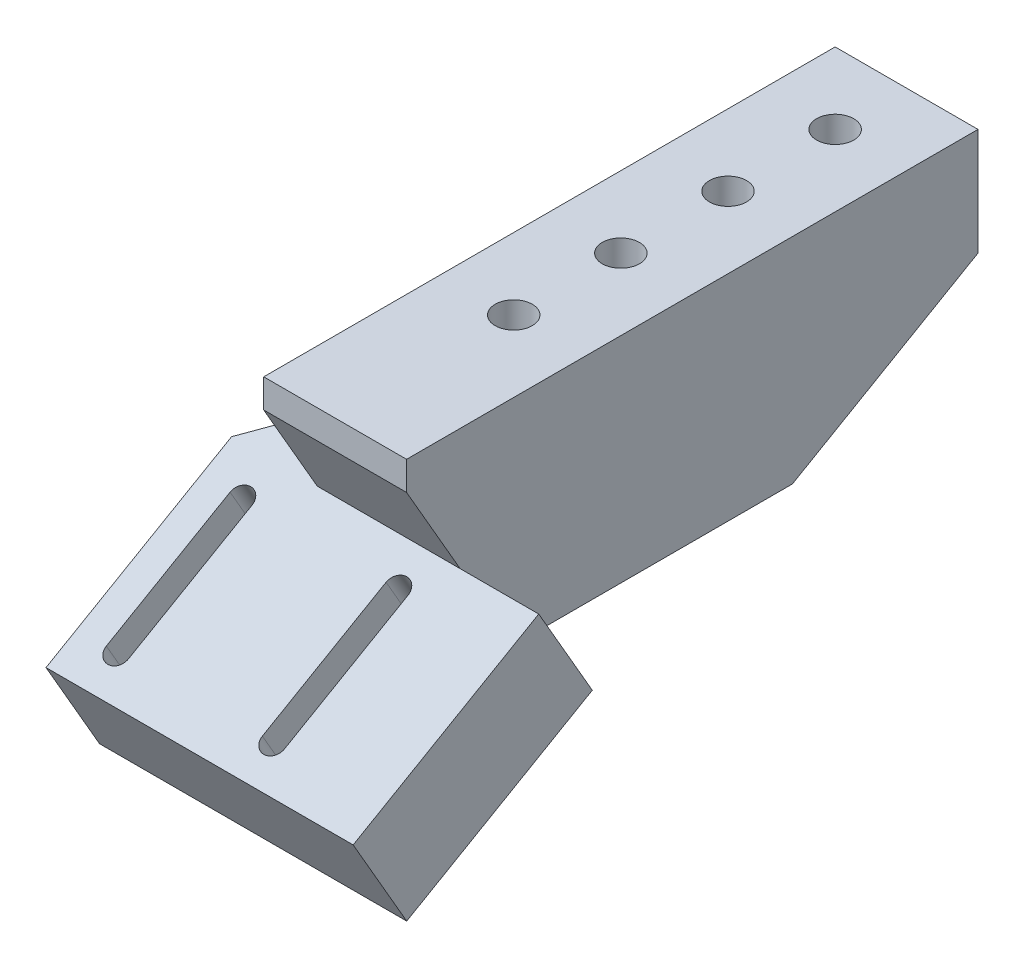
SolidWorks part; units mm, degrees
ref_plane "Front Plane" through (0, 0, 0) normal (0, 0, 1) x (1, 0, 0)
ref_plane "Top Plane" through (0, 0, 0) normal (0, 1, 0) x (1, 0, 0)
ref_plane "Right Plane" through (0, 0, 0) normal (1, 0, 0) x (0, 0, -1)
sketch "Sketch1" plane through (0, 0, 0) normal (1, 0, 0) x (0, 0, -1)
  line L1 (-40, 15) -> (40, 15)
  line L2 (-40, 15) -> (-40, -15)
  line L3 (-40, -15) -> (40, -15)
  line L4 (40, 15) -> (40, -15)
  line L5 (-40, 15) -> (40, -15) construction
  line L6 (-40, -15) -> (40, 15) construction
  point P0 (0, 0)
  dimension "D1" = 30
  dimension "D2" = 80
extrude "Boss-Extrude1" add sketch "Sketch1" against normal blind 20
chamfer "Chamfer1" distance 15 angle 60 1 edges at (-10, -15, 40) first distance on face at (-10, -15, 0)
sketch "Sketch2" plane through (0, -14.5753, 25.2452) normal (0, -0.5, 0.866) x (1, 0, 0)
  line L0 (-10, 29.5096) -> (-10, -0.4904) construction
  line L2 (-20, 29.5096) -> (0, 29.5096) construction
  line L7 (0, -0.4904) -> (-20, -0.4904) construction
  line L8 (-32, -0.4904) -> (11, -0.4904)
  line L13 (-32, -0.4904) -> (-32, 14.5096)
  line L14 (11, -0.4904) -> (11, 14.5096)
  line L15 (-32, 14.5096) -> (11, 14.5096)
  line L16 (0, 29.5096) -> (0, -0.4904) construction
  line L17 (-20, -0.4904) -> (-20, 29.5096) construction
  dimension "D1" = 11
  dimension "D2" = 12
  dimension "D3" = 15
extrude "Boss-Extrude2" add sketch "Sketch2" along normal blind 30
sketch "Sketch3" plane through (0, 12.5657, 7.2548) normal (0, 0.866, 0.5) x (1, 0, 0)
  line L0 (-26.33, -34.1506) -> (-26.33, -54.1506) construction
  line L3 (-24.78, -34.1506) -> (-24.78, -54.1506)
  line L4 (-27.88, -34.1506) -> (-27.88, -54.1506)
  line L5 (-32, -44.1506) -> (11, -44.1506) construction
  line L6 (-32, -59.1506) -> (-32, -29.1506) construction
  line L7 (11, -59.1506) -> (11, -29.1506) construction
  line L8 (-4.49, -34.1506) -> (-4.49, -54.1506) construction
  line L9 (-2.94, -34.1506) -> (-2.94, -54.1506)
  line L10 (-6.04, -34.1506) -> (-6.04, -54.1506)
  arc A2 (-24.78, -34.1506) -> (-27.88, -34.1506) centre (-26.33, -34.1506) ccw
  arc A3 (-27.88, -54.1506) -> (-24.78, -54.1506) centre (-26.33, -54.1506) ccw
  arc A4 (-2.94, -34.1506) -> (-6.04, -34.1506) centre (-4.49, -34.1506) ccw
  arc A5 (-6.04, -54.1506) -> (-2.94, -54.1506) centre (-4.49, -54.1506) ccw
  point P2 (-26.33, -44.1506)
  point P16 (-4.49, -44.1506)
  dimension "D1" = 1.55
  dimension "D2" = 20
  dimension "D3" = 5.67
extrude "Cut-Extrude1" cut sketch "Sketch3" against normal up to next
sketch "Sketch4" plane through (0, -0.4247, -0.2452) normal (0, -0.866, -0.5) x (1, 0, 0)
  line L0 (-27.88, 44.1506) -> (-24.78, 44.1506) construction
  line L1 (-27.88, 54.1506) -> (-27.88, 34.1506) construction
  line L2 (-24.78, 34.1506) -> (-24.78, 54.1506) construction
  line L3 (-26.33, 54.1506) -> (-26.33, 34.1506) construction
  line L4 (-23.58, 54.1506) -> (-23.58, 34.1506)
  line L5 (-29.08, 54.1506) -> (-29.08, 34.1506)
  line L6 (-4.49, 54.1506) -> (-4.49, 34.1506) construction
  line L7 (-1.74, 54.1506) -> (-1.74, 34.1506)
  line L8 (-7.24, 54.1506) -> (-7.24, 34.1506)
  arc A0 (-23.58, 54.1506) -> (-29.08, 54.1506) centre (-26.33, 54.1506) ccw
  arc A1 (-29.08, 34.1506) -> (-23.58, 34.1506) centre (-26.33, 34.1506) ccw
  arc A2 (-1.74, 54.1506) -> (-7.24, 54.1506) centre (-4.49, 54.1506) ccw
  arc A3 (-7.24, 34.1506) -> (-1.74, 34.1506) centre (-4.49, 34.1506) ccw
  point P8 (-26.33, 44.1506)
  point P14 (-26.33, 44.1506)
  point P17 (-4.49, 44.1506)
  dimension "D1" = 2.75
extrude "Cut-Extrude2" cut sketch "Sketch4" against normal blind 3
sketch "Sketch5" plane through (0, 12.5657, 7.2548) normal (0, 0.866, 0.5) x (1, 0, 0)
  line L0 (-32, -29.1506) -> (-20, -29.1506)
  line L1 (-32, -29.1506) -> (-32, -17.1506)
  line L2 (-20, -29.1506) -> (-20, -17.1506)
  line L3 (-32, -17.1506) -> (-20, -17.1506)
extrude "Boss-Extrude3" add sketch "Sketch5" against normal up to surface (15 mm away) up to face at (-26.33, -22.5, 37.9904)
chamfer "Chamfer2" distance 12 angle 45 1 edges at (-32, -2.5048, 18.3577)
sketch "Sketch6" plane through (0, -15, 0) normal (0, -1, 0) x (1, 0, 0)
  line L0 (-10, 25) -> (-10, -40) construction
  line L3 (0, 25) -> (-20, 25) construction
  line L7 (-20, -40) -> (0, -40) construction
  circle A0 centre (-10, -30) radius 2.6
  circle A2 centre (-10, -15) radius 2.6
  circle A3 centre (-10, 0) radius 2.6
  circle A4 centre (-10, 15) radius 2.6
  dimension "D1" = 5.2
  dimension "D2" = 10
extrude "Cut-Extrude3" cut sketch "Sketch6" against normal up to next
sketch "Sketch7" plane through (0, -15, 0) normal (0, -1, 0) x (1, 0, 0)
  circle A0 centre (-10, 15) radius 5.5
  circle A1 centre (-10, 0) radius 5.5
  circle A2 centre (-10, -15) radius 5.5
  circle A3 centre (-10, -30) radius 5.5
  dimension "D1" = 11
extrude "Cut-Extrude4" cut sketch "Sketch7" against normal blind 20
chamfer "Chamfer3" distance 15 angle 60 1 edges at (-10, -15, -40) first distance on face at (-10, 0, -40)
